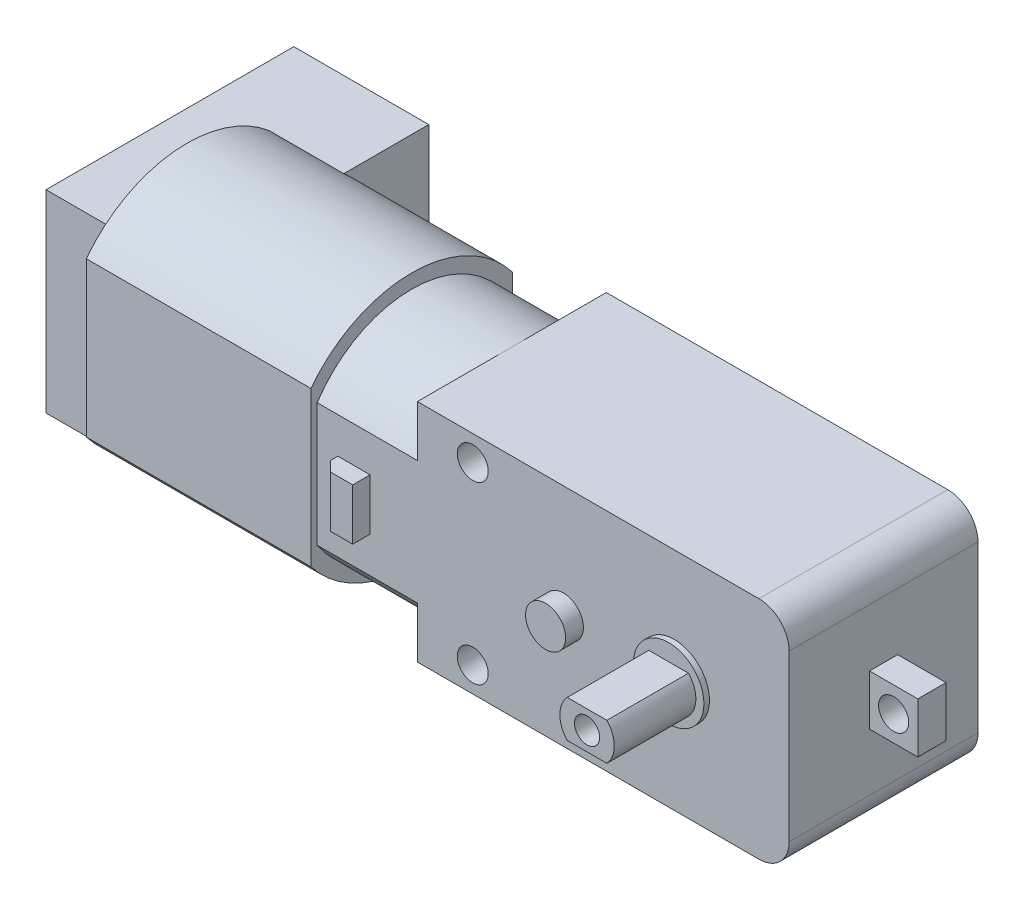
SolidWorks part; units mm, degrees
ref_plane "Alzado" through (0, 0, 0) normal (0, 0, 1) x (1, 0, 0)
ref_plane "Planta" through (0, 0, 0) normal (0, 1, 0) x (1, 0, 0)
ref_plane "Vista lateral" through (0, 0, 0) normal (1, 0, 0) x (0, 0, -1)
sketch "Croquis1" plane through (0, 0, 0) normal (0, 0, 1) x (1, 0, 0)
  line L0 (0, 0) -> (-11, 0) construction
  line L1 (0, 0) -> (11.41, 0) construction
  line L2 (11.41, -11.2) -> (11.41, 11.2)
  line L3 (11.41, 11.2) -> (-25.49, 11.2)
  line L4 (-25.49, 11.2) -> (-25.49, -11.2)
  line L5 (-25.49, 0) -> (-11, 0) construction
  line L6 (11.41, 2.5) -> (16.21, 2.5)
  line L7 (16.21, 2.5) -> (16.21, -2.5)
  line L8 (11.41, -2.5) -> (16.21, -2.5)
  line L9 (11.41, -11.2) -> (-25.49, -11.2)
  line L10 (-35.44, 11.2) -> (-35.44, 12.6)
  line L11 (-25.49, 11.2) -> (-35.44, 11.2)
  line L12 (-25.49, 11.2) -> (-25.49, -11.2)
  line L13 (-25.49, -11.2) -> (-35.44, -11.2) construction
  line L14 (-35.44, 11.2) -> (-35.44, -11.2) construction
  line L15 (-35.44, 12.6) -> (-57.74, 12.6)
  line L16 (-57.74, 12.6) -> (-57.74, -12.6) construction
  line L17 (-57.74, 9.6) -> (-63.74, 9.6)
  line L18 (-63.74, 9.6) -> (-63.74, -9.6)
  line L19 (-57.74, -9.6) -> (-63.74, -9.6)
  line L20 (-35.44, -12.6) -> (-57.74, -12.6) construction
  line L21 (11.41, 0) -> (16.21, 0) construction
  line L22 (-35.44, -11.2) -> (-35.44, -12.6) construction
  line L23 (-25.49, 0) -> (-31.79, 0) construction
  line L24 (-25.49, 0) -> (-57.74, 0)
  line L25 (-30.19, -2.55) -> (-33.39, -2.55)
  line L26 (-30.19, -2.55) -> (-30.19, 2.55)
  line L27 (-30.19, 2.55) -> (-33.39, 2.55)
  line L28 (-33.39, -2.55) -> (-33.39, 2.55)
  line L29 (-30.19, -2.55) -> (-33.39, 2.55) construction
  line L30 (-30.19, 2.55) -> (-33.39, -2.55) construction
  line L31 (-57.74, 9.6) -> (-50.34, 9.6)
  line L32 (-57.74, 9.6) -> (-57.74, -9.6)
  line L33 (-57.74, -9.6) -> (-50.34, -9.6)
  line L34 (-50.34, 9.6) -> (-50.34, -9.6)
  line L35 (-57.74, 12.6) -> (-57.74, 0)
  circle A0 centre (0, 0) radius 2.7
  circle A1 centre (-11, 0) radius 1.99
  circle A2 centre (-20, 8.7) radius 1.54
  circle A3 centre (13.81, 0) radius 1.495
  circle A4 centre (-20, -8.7) radius 1.54
  point P17 (16.21, 0)
  point P31 (-63.74, 0)
  point P33 (-57.74, 0)
  dimension "D1" = 5.4
  dimension "D3" = 3.98
  dimension "D4" = 3.08
  dimension "D15" = 2.99
  dimension "D2" = 11
  dimension "D5" = 9
  dimension "D6" = 24.81
  dimension "D7" = 22.4
  dimension "D8" = 5
  dimension "D9" = 17.4
  dimension "D10" = 22.3
  dimension "D11" = 25.2
  dimension "D12" = 19.2
  dimension "D13" = 79.95
  dimension "D14" = 75.15
  dimension "D16" = 19.19
  dimension "D17" = 6
  dimension "D18" = 36.9
  dimension "D19" = 3.2
  dimension "D20" = 5.1
  dimension "D21" = 13.4
extrude "Saliente-Extruir1" add sketch "Croquis1" along normal mid plane 18.75 contours L9 L2 L3 L4 A0 A1 A2 A4 | A0 | A1 region at (-6.9355, 0, 0) region at (0, 0, 0) region at (-11, 0, 0)
extrude "Saliente-Extruir2" add sketch "Croquis1<3>" along normal blind 8.65 from surface contours A0 starting at face at (-7.04, 0, 9.375)
sketch "Croquis1<3>" plane through (0, 0, 0) normal (0, 0, 1) x (1, 0, 0) same geometry as "Croquis1"
extrude "Saliente-Extruir3" add sketch "Croquis1<5>" along normal blind 1.77 from surface contours A1 region at (-11, 0, 0) starting at face at (2.7, 0, 9.375)
sketch "Croquis1<5>" plane through (0, 0, 0) normal (0, 0, 1) x (1, 0, 0) same geometry as "Croquis1"
sketch "Croquis2" plane through (0, 0, 0) normal (1, 0, 0) x (0, 0, -1)
  line L0 (-18.025, 2.7) -> (-18.025, -2.7) construction
  line L1 (-18.025, 2.7) -> (-9.375, 2.7)
  line L2 (-18.025, 2.7) -> (-18.025, 1.85)
  line L3 (-18.025, 1.85) -> (-9.375, 1.85)
  line L4 (-9.375, 2.7) -> (-9.375, 1.85)
  line L5 (-9.375, -11.2) -> (-9.375, 11.2) construction
  line L6 (-1000, 0) -> (49000, 0) construction
  line L7 (-9.375, -2.7) -> (-9.375, -1.85)
  line L8 (-18.025, -1.85) -> (-9.375, -1.85)
  line L9 (-18.025, -2.7) -> (-18.025, -1.85)
  line L10 (-18.025, -2.7) -> (-9.375, -2.7)
  dimension "D1" = 3.7
extrude "Cortar-Extruir1" cut sketch "Croquis2" against normal mid plane 6.77 contours L2 L1 L4 L3 | L7 L8 L9 L10
extrude "Saliente-Extruir4" add sketch "Croquis1<6>" along normal mid plane 2.8 contours L2 L8 L7 L6 A3 region at (11.4793, 0, 0)
sketch "Croquis1<6>" plane through (0, 0, 0) normal (0, 0, 1) x (1, 0, 0) same geometry as "Croquis1"
revolve "Revolución1" add sketch "Croquis1<8>" angle 360 about L24 region at (-39.5488, 6.5221, 0) region at (-31.79, 1.275, 0) region at (-54.04, 4.8, 0)
sketch "Croquis1<8>" plane through (0, 0, 0) normal (0, 0, 1) x (1, 0, 0) same geometry as "Croquis1"
sketch "Croquis3" plane through (0, 0, 0) normal (0, 1, 0) x (1, 0, 0)
  line L0 (0, 0) -> (-25.49, 0) construction
  line L1 (-35.44, -12.6) -> (-35.44, 12.6) construction
  line L2 (-35.44, 9.375) -> (-25.49, 9.375)
  line L3 (-35.44, 9.375) -> (-35.44, -9.375)
  line L4 (-35.44, -9.375) -> (-25.49, -9.375)
  line L5 (-25.49, 9.375) -> (-25.49, -9.375)
  line L6 (-25.49, 0) -> (-35.44, 0) construction
  line L7 (-57.74, 12.6) -> (-57.74, -12.6) construction
  line L8 (-57.74, 10) -> (-35.44, 10)
  line L9 (-57.74, 10) -> (-57.74, -10)
  line L10 (-57.74, -10) -> (-35.44, -10)
  line L11 (-35.44, 10) -> (-35.44, -10)
  line L13 (-57.74, 10) -> (-35.44, 10)
  line L14 (-57.74, 10) -> (-57.74, 12.6)
  line L15 (-57.74, 12.6) -> (-35.44, 12.6)
  line L16 (-35.44, 10) -> (-35.44, 12.6)
  line L17 (-57.74, -10) -> (-35.44, -10)
  line L18 (-57.74, -10) -> (-57.74, -12.6)
  line L19 (-57.74, -12.6) -> (-35.44, -12.6)
  line L20 (-35.44, -10) -> (-35.44, -12.6)
  line L21 (-35.44, -9.375) -> (-25.49, -9.375)
  line L22 (-35.44, -9.375) -> (-35.44, -11.2)
  line L23 (-35.44, -11.2) -> (-25.49, -11.2)
  line L24 (-25.49, -9.375) -> (-25.49, -11.2)
  line L25 (-35.44, 9.375) -> (-25.49, 9.375)
  line L26 (-35.44, 9.375) -> (-35.44, 11.2)
  line L27 (-35.44, 11.2) -> (-25.49, 11.2)
  line L28 (-25.49, 9.375) -> (-25.49, 11.2)
  dimension "D1" = 18.75
  dimension "D2" = 20
extrude "Cortar-Extruir2" cut sketch "Croquis3" against normal through all both and the other way through all contours L2 L28 L27 L16 L11 | L8 L16 L15 L14 | L20 L10 L18 L19 | L24 L4 L11 L20 L23 region at (-30.465, 0, -10.2875) region at (-30.465, 0, 10.2875) region at (-46.59, 0, -11.3) region at (-46.59, 0, 11.3)
extrude "Saliente-Extruir5" add sketch "Croquis1<10>" along normal mid plane 22.2 contours L25 L28 L27 L26
sketch "Croquis1<10>" plane through (0, 0, 0) normal (0, 0, 1) x (1, 0, 0) same geometry as "Croquis1"
extrude "Saliente-Extruir6" add sketch "Croquis1<11>" against normal blind 16.6 and the other way blind 8 contours L32 L17 L18 L19 | L34 L31 L32 L24 | L34 L24 L32 L33 region at (-54.04, -4.8, 0) region at (-54.04, 4.8, 0) region at (-60.74, 0, 0)
sketch "Croquis1<11>" plane through (0, 0, 0) normal (0, 0, 1) x (1, 0, 0) same geometry as "Croquis1"
hole_wizard "Taladro roscado M3x0.51" positions "Croquis4" profile "Croquis5" tap size "M3x0.5" standard "Ansi Metric"
sketch "Croquis4" plane through (0, 0, 18.025) normal (0, 0, 1) x (1, 0, 0)
  point P0 (0, 0)
cosmetic thread "Rosca de taladro1" parameters "D1"=27.4, "D2"=3
sketch "Croquis5" plane through (0, 0, 18.025) normal (1, 0, 0) x (0, -1, 0)
  line L0 (0, 0) -> (0, 6.7511)
  line L1 (0, 6.7511) -> (1.25, 6)
  line L2 (1.25, 6) -> (1.25, 0)
  line L5 (1.25, 0) -> (0, 0)
  line L10 (0, 6.7511) -> (-1.25, 6) construction
  line L11 (0, -6.35) -> (0, 107.95) construction
  dimension "Diámetro de perforador para roscar" = 2.5
  dimension "Profundidad de perforador para roscar" = 6
  dimension "Ángulo de perforador" = 118
fillet "Redondeo1" radius 3 2 edges at (11.41, -11.2, 0) (11.41, 11.2, 0)
sketch "Croquis6" plane through (0, 0, 0) normal (0, 0, 1) x (1, 0, 0)
  circle A0 centre (0, 0) radius 3.5
  dimension "D1" = 7
extrude "Saliente-Extruir7" add sketch "Croquis6" along normal blind 0.55 from surface starting at face at (0, 0, 9.375)
chamfer "Chaflán1" distance 1 angle 45 1 edges at (-33.39, 0, 11.1)
